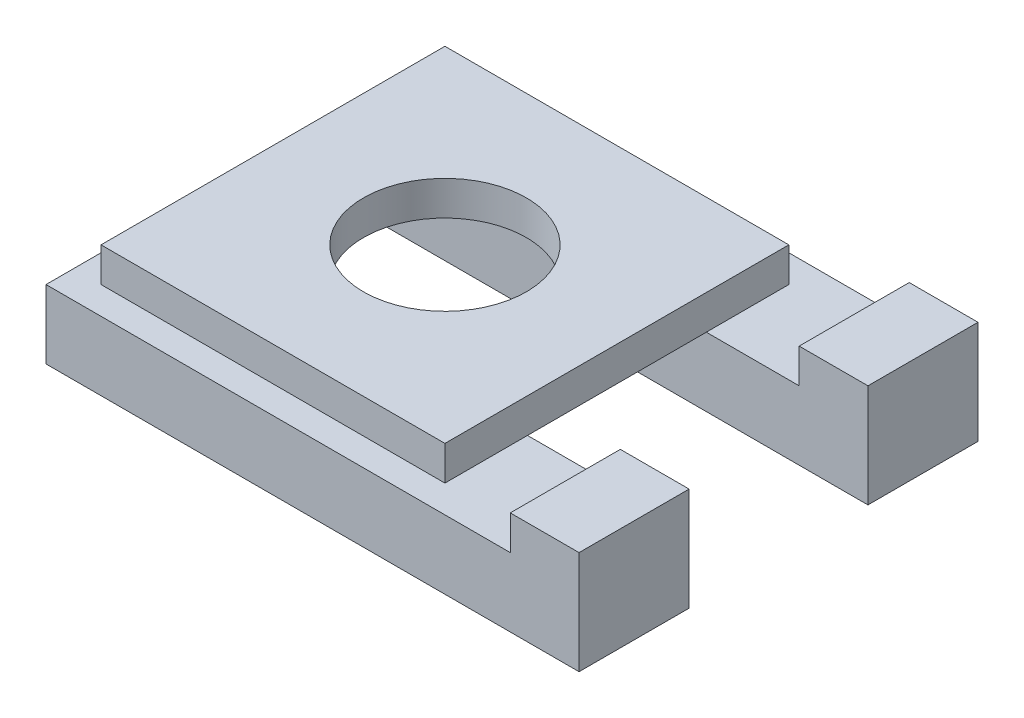
SolidWorks part; units mm, degrees
ref_plane "Front Plane" through (0, 0, 0) normal (0, 0, 1) x (1, 0, 0)
ref_plane "Top Plane" through (0, 0, 0) normal (0, 1, 0) x (1, 0, 0)
ref_plane "Right Plane" through (0, 0, 0) normal (1, 0, 0) x (0, 0, -1)
sketch "Sketch1" plane through (0, 0, 0) normal (0, 1, 0) x (1, 0, 0)
  line L1 (-50, -50) -> (50, -50)
  line L2 (-50, -50) -> (-50, 50)
  line L3 (-50, 50) -> (50, 50)
  line L4 (50, -50) -> (50, 50)
  line L5 (-50, -50) -> (50, 50) construction
  line L6 (-50, 50) -> (50, -50) construction
  circle A0 centre (0, 0) radius 23.6821
  dimension "D1" = 100
  dimension "D2" = 100
extrude "Boss-Extrude1" add sketch "Sketch1" along normal blind 10
sketch "Sketch2" plane through (0, 0, 0) normal (0, -1, 0) x (1, 0, 0)
  line L0 (-64.9019, 0) -> (76.217, 0) construction
  line L1 (-58, 58) -> (97, 58)
  line L2 (-58, 58) -> (-58, 26)
  line L3 (-58, 26) -> (97, 26)
  line L4 (97, 58) -> (97, 26)
  line L5 (-50, -50) -> (-50, 50) construction
  line L6 (-50, 50) -> (50, 50) construction
  line L7 (77, 58) -> (77, 26)
  line L8 (77, -58) -> (77, -26)
  line L9 (97, -58) -> (97, -26)
  line L10 (-58, -26) -> (97, -26)
  line L11 (-58, -58) -> (-58, -26)
  line L12 (-58, -58) -> (97, -58)
  line M7 (50, -50) -> (50, 50)
  line M8 (50, 50) -> (-50, 50)
  line M9 (-50, 50) -> (-50, -50)
  line M10 (-50, -50) -> (50, -50)
  dimension "D1" = 32
  dimension "D2" = 155
  dimension "D3" = 8
  dimension "D4" = 8
  dimension "D5" = 20
extrude "Boss-Extrude2" add sketch "Sketch2" along normal blind 20 contours L3 M9 M7 M8 | L7 L1 L2 L3 M9 M8 M7 | L11 L12 L8 L10 M7 M10 M9 | L10 M9 M10 M7 region at (9.5, 0, 56.6126) region at (0, 0, 38) region at (-51.3874, 0, -38) region at (0, 0, -38)
extrude "Boss-Extrude3" add sketch "Sketch2<3>" along normal blind 20 and the other way blind 10 contours L8 L12 L9 L10 | L1 L7 L3 L4 region at (87, 0, 42) region at (87, 0, -42)
sketch "Sketch2<3>" plane through (0, 0, 0) normal (0, -1, 0) x (1, 0, 0) same geometry as "Sketch2"
